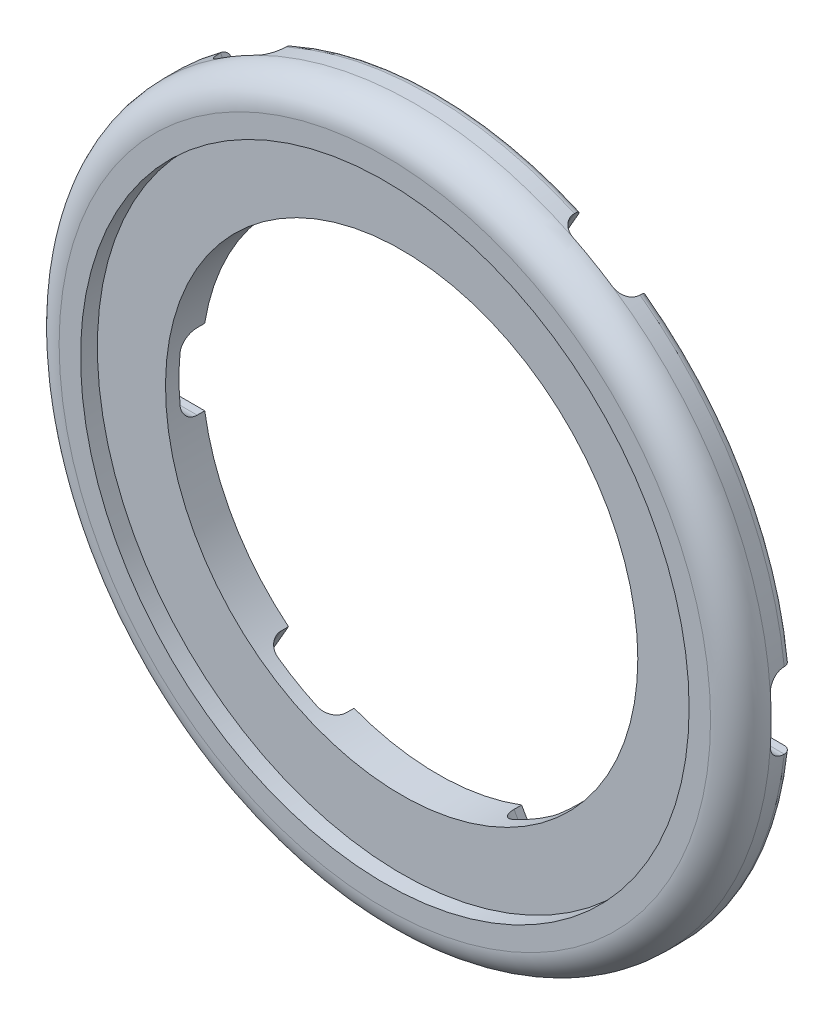
SolidWorks part; units mm, degrees
ref_plane "前视基准面" through (0, 0, 0) normal (0, 0, 1) x (1, 0, 0)
ref_plane "上视基准面" through (0, 0, 0) normal (0, 1, 0) x (1, 0, 0)
ref_plane "右视基准面" through (0, 0, 0) normal (1, 0, 0) x (0, 0, -1)
sketch "草图1" plane through (0, 0, 0) normal (0, 0, 1) x (1, 0, 0)
  circle A20 centre (0, 0) radius 23.5157 construction
  circle A21 centre (0, 0) radius 23.5157
  circle A22 centre (0, 0) radius 15.6 construction
  circle A23 centre (0, 0) radius 15.6
extrude "凸台-拉伸1" add sketch "草图1" along normal blind 3.5
sketch "草图2" plane through (0, 0, 0) normal (0, 0, -1) x (-1, 0, 0)
  circle A0 centre (0.0014, 17.6178) radius 1.15
  circle A1 centre (15.2581, 8.8077) radius 1.15
  circle A2 centre (15.2567, -8.8101) radius 1.15
  circle A3 centre (-0.0014, -17.6178) radius 1.15
  circle A4 centre (-15.2581, -8.8077) radius 1.15
  circle A5 centre (-15.2567, 8.8101) radius 1.15
  point P15 (0, 0)
  dimension "D1" = 2.3
extrude "切除-拉伸1" cut sketch "草图2" against normal blind 2.2
sketch "草图3" plane through (0, 0, 3.5) normal (0, 0, 1) x (1, 0, 0)
  circle A0 centre (0, 0) radius 20.1
  dimension "D1" = 40.2
extrude "切除-拉伸2" cut sketch "草图3" against normal blind 1.11
fillet "圆角1" radius 2 1 edges at (23.5157, 0, 3.5)
sketch "草图5" plane through (0, 0, 0) normal (0, 0, -1) x (-1, 0, 0)
  line L1 (-23.3824, 2.5) -> (-15.3984, 2.5)
  line L3 (-23.3824, -2.5) -> (-15.3984, -2.5)
  line L5 (-9.5261, 21.4998) -> (-5.5341, 14.5854)
  line L6 (-13.8563, 18.9998) -> (-9.8643, 12.0854)
  line L7 (13.8563, 18.9998) -> (9.8643, 12.0854)
  line L8 (9.5261, 21.4998) -> (5.5341, 14.5854)
  line L9 (23.3824, -2.5) -> (15.3984, -2.5)
  line L10 (23.3824, 2.5) -> (15.3984, 2.5)
  line L11 (9.5261, -21.4998) -> (5.5341, -14.5854)
  line L12 (13.8563, -18.9998) -> (9.8643, -12.0854)
  line L13 (-13.8563, -18.9998) -> (-9.8643, -12.0854)
  line L14 (-9.5261, -21.4998) -> (-5.5341, -14.5854)
  arc A0 (-15.3984, 2.5) -> (-15.3984, -2.5) centre (0, 0) ccw
  arc A1 (-23.3824, 2.5) -> (-23.3824, -2.5) centre (0, 0) ccw
  arc A2 (-5.5341, 14.5854) -> (-9.8643, 12.0854) centre (0, 0) ccw
  arc A3 (-9.5261, 21.4998) -> (-13.8563, 18.9998) centre (0, 0) ccw
  arc A4 (9.8643, 12.0854) -> (5.5341, 14.5854) centre (0, 0) ccw
  arc A5 (13.8563, 18.9998) -> (9.5261, 21.4998) centre (0, 0) ccw
  arc A6 (15.3984, -2.5) -> (15.3984, 2.5) centre (0, 0) ccw
  arc A7 (23.3824, -2.5) -> (23.3824, 2.5) centre (0, 0) ccw
  arc A8 (5.5341, -14.5854) -> (9.8643, -12.0854) centre (0, 0) ccw
  arc A9 (9.5261, -21.4998) -> (13.8563, -18.9998) centre (0, 0) ccw
  arc A10 (-9.8643, -12.0854) -> (-5.5341, -14.5854) centre (0, 0) ccw
  arc A11 (-13.8563, -18.9998) -> (-9.5261, -21.4998) centre (0, 0) ccw
  point P0 (0, 0)
  point P30 (0, 0)
  dimension "D1" = 6
  dimension "D2" = 5
extrude "切除-拉伸3" cut sketch "草图5" against normal blind 1.5
fillet "圆角2" radius 1 12 edges at (-11.8603, 15.5426, 1.5) (-7.5301, 18.0426, 1.5) (-19.3904, -2.5, 1.5) (-19.3904, 2.5, 1.5) (-11.8603, -15.5426, 1.5) (-7.5301, -18.0426, 1.5) (11.8603, -15.5426, 1.5) (7.5301, -18.0426, 1.5) (19.3904, -2.5, 1.5) (19.3904, 2.5, 1.5) (11.8603, 15.5426, 1.5) (7.5301, 18.0426, 1.5)
fillet "圆角3" radius 0.5 6 edges at (-20.3652, 11.7578, 0) (-20.3652, -11.7578, 0) (0, -23.5157, 0) (20.3652, -11.7578, 0) (0, 23.5157, 0) (20.3652, 11.7578, 0)
